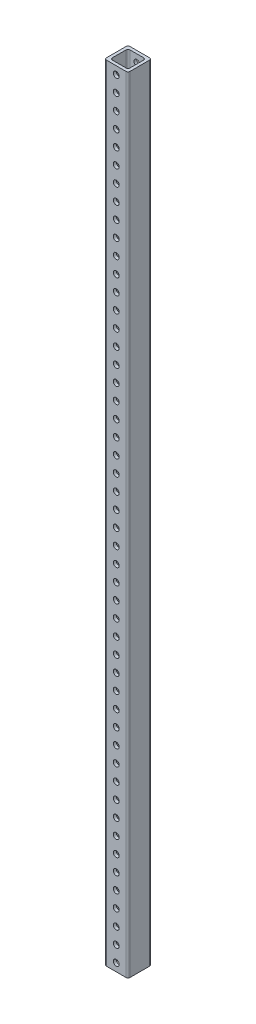
SolidWorks part; units mm, degrees
ref_plane "Front Plane" through (0, 0, 0) normal (0, 0, 1) x (1, 0, 0)
ref_plane "Top Plane" through (0, 0, 0) normal (0, 1, 0) x (1, 0, 0)
ref_plane "Right Plane" through (0, 0, 0) normal (1, 0, 0) x (0, 0, -1)
sketch "Sketch1" plane through (0, 0, 0) normal (0, 1, 0) x (1, 0, 0)
  line L0 (4.7625, -4.7625) -> (33.3375, -4.7625)
  line L1 (0, 0) -> (38.1, 0)
  line L2 (0, 0) -> (0, -38.1)
  line L3 (0, -38.1) -> (38.1, -38.1)
  line L4 (38.1, 0) -> (38.1, -38.1)
  line L5 (33.3375, -4.7625) -> (33.3375, -33.3375)
  line L6 (4.7625, -33.3375) -> (33.3375, -33.3375)
  line L7 (4.7625, -4.7625) -> (4.7625, -33.3375)
  dimension "D1" = 38.1
  dimension "D2" = 38.1
  dimension "D3" = 4.7625
extrude "Boss-Extrude1" add sketch "Sketch1" along normal blind 1270
fillet "Fillet1" radius 3.175 8 edges at (33.3375, 635, 4.7625) (33.3375, 635, 33.3375) (4.7625, 635, 4.7625) (4.7625, 635, 33.3375) (0, 635, 0) (38.1, 635, 0) (0, 635, 38.1) (38.1, 635, 38.1)
sketch "Sketch2" plane through (0, 0, 38.1) normal (0, 0, 1) x (1, 0, 0)
  line L0 (19.05, 1270) -> (19.05, 0) construction
  line L1 (3.175, 1270) -> (34.925, 1270) construction
  line L2 (3.175, 0) -> (34.925, 0) construction
  circle A0 centre (19.05, 1257.3) radius 4.7625
  circle A1 centre (19.05, 1231.9) radius 4.7625
  circle A2 centre (19.05, 1206.5) radius 4.7625
  circle A3 centre (19.05, 1181.1) radius 4.7625
  circle A4 centre (19.05, 1155.7) radius 4.7625
  circle A5 centre (19.05, 1130.3) radius 4.7625
  circle A6 centre (19.05, 1104.9) radius 4.7625
  circle A7 centre (19.05, 1079.5) radius 4.7625
  circle A8 centre (19.05, 1054.1) radius 4.7625
  circle A9 centre (19.05, 1028.7) radius 4.7625
  circle A10 centre (19.05, 1003.3) radius 4.7625
  circle A11 centre (19.05, 977.9) radius 4.7625
  circle A12 centre (19.05, 952.5) radius 4.7625
  circle A13 centre (19.05, 927.1) radius 4.7625
  circle A14 centre (19.05, 901.7) radius 4.7625
  circle A15 centre (19.05, 876.3) radius 4.7625
  circle A16 centre (19.05, 850.9) radius 4.7625
  circle A17 centre (19.05, 825.5) radius 4.7625
  circle A18 centre (19.05, 800.1) radius 4.7625
  circle A19 centre (19.05, 774.7) radius 4.7625
  circle A20 centre (19.05, 749.3) radius 4.7625
  circle A21 centre (19.05, 723.9) radius 4.7625
  circle A22 centre (19.05, 698.5) radius 4.7625
  circle A23 centre (19.05, 673.1) radius 4.7625
  circle A24 centre (19.05, 647.7) radius 4.7625
  circle A25 centre (19.05, 622.3) radius 4.7625
  circle A26 centre (19.05, 596.9) radius 4.7625
  circle A27 centre (19.05, 571.5) radius 4.7625
  circle A28 centre (19.05, 546.1) radius 4.7625
  circle A29 centre (19.05, 520.7) radius 4.7625
  circle A30 centre (19.05, 495.3) radius 4.7625
  circle A31 centre (19.05, 469.9) radius 4.7625
  circle A32 centre (19.05, 444.5) radius 4.7625
  circle A33 centre (19.05, 419.1) radius 4.7625
  circle A34 centre (19.05, 393.7) radius 4.7625
  circle A35 centre (19.05, 368.3) radius 4.7625
  circle A36 centre (19.05, 342.9) radius 4.7625
  circle A37 centre (19.05, 317.5) radius 4.7625
  circle A38 centre (19.05, 292.1) radius 4.7625
  circle A39 centre (19.05, 266.7) radius 4.7625
  circle A40 centre (19.05, 241.3) radius 4.7625
  circle A41 centre (19.05, 215.9) radius 4.7625
  circle A42 centre (19.05, 190.5) radius 4.7625
  circle A43 centre (19.05, 165.1) radius 4.7625
  circle A44 centre (19.05, 139.7) radius 4.7625
  circle A45 centre (19.05, 114.3) radius 4.7625
  circle A46 centre (19.05, 88.9) radius 4.7625
  circle A47 centre (19.05, 63.5) radius 4.7625
  circle A48 centre (19.05, 38.1) radius 4.7625
  circle A49 centre (19.05, 12.7) radius 4.7625
  dimension "D1" = 9.525
  dimension "D2" = 12.7
  dimension "D3" = 50
extrude "Cut-Extrude1" cut sketch "Sketch2" against normal blind 50.8
